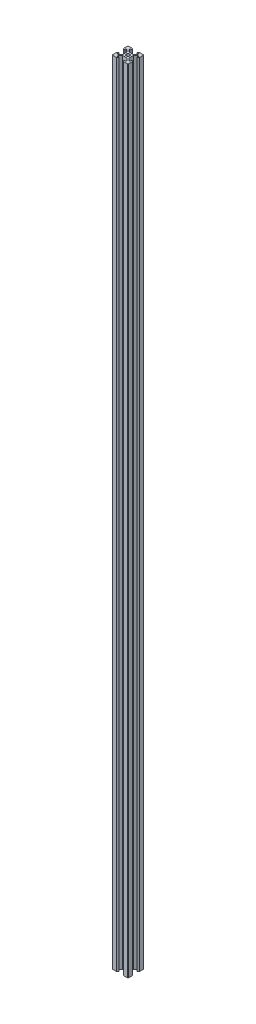
SolidWorks part; units mm, degrees
ref_plane "Front Plane" through (0, 0, 0) normal (0, 0, 1) x (1, 0, 0)
ref_plane "Top Plane" through (0, 0, 0) normal (0, 1, 0) x (1, 0, 0)
ref_plane "Right Plane" through (0, 0, 0) normal (1, 0, 0) x (0, 0, -1)
sketch "Sketch1" plane through (0, 0, 0) normal (0, 1, 0) x (1, 0, 0)
  line L0 (-2.1465, 12.2219) -> (22.938, 12.2219) construction
  line L1 (7.155, 13.9) -> (4.5, 16.555)
  line L2 (0.5, 0) -> (5.42, 0)
  line L3 (0, 0.5) -> (0, 5.42)
  line L4 (0.5, 20) -> (5.42, 20)
  line L5 (20, 0.5) -> (20, 19.5)
  line L6 (7.155, 13.9) -> (12.8341, 13.9)
  line L7 (6.1, 12.845) -> (6.1, 7.1491)
  line L8 (7.1445, 6.1) -> (12.8546, 6.1)
  line L9 (13.9, 12.8445) -> (13.9, 7.1491)
  line L10 (0, 20) -> (4.5, 20)
  line L11 (0, 20) -> (0, 15.5)
  line L12 (1.8, 15.5) -> (3.445, 15.5)
  line L13 (4.5, 18.2) -> (4.5, 16.555)
  line L14 (6.1, 12.845) -> (6.0943, 12.8393)
  line L15 (3.445, 15.5) -> (3.4393, 15.4943)
  line L16 (6.0943, 12.8393) -> (3.4393, 15.4943)
  line L17 (5.42, 20) -> (6.875, 18.545)
  line L18 (4.5, 20) -> (5.42, 20)
  line L19 (6.875, 20) -> (19.5, 20)
  line L20 (4.5, 18.2) -> (6.875, 18.2)
  line L21 (6.875, 20) -> (6.875, 18.2)
  line L22 (0, 14.58) -> (1.46, 13.12)
  line L23 (15.5, 18.2) -> (15.5, 16.555)
  line L24 (0, 15.5) -> (0, 13.12)
  line L25 (0, 13.12) -> (1.8, 13.12)
  line L26 (1.8, 15.5) -> (1.8, 13.12)
  line L27 (16.5507, 15.5) -> (18.2, 15.5)
  line L28 (15.5, 18.2) -> (13.12, 18.2)
  line L29 (13.12, 18.2) -> (13.12, 18.545)
  line L30 (13.12, 18.545) -> (14.575, 20)
  line L31 (18.2, 15.5) -> (18.2, 13.12)
  line L32 (18.2, 13.12) -> (18.5344, 13.12)
  line L33 (18.5344, 13.12) -> (20, 14.58)
  line L34 (12.8341, 13.9) -> (15.5, 16.555)
  line L35 (18.2, 4.5) -> (16.5585, 4.5)
  line L36 (16.5507, 15.5) -> (16.5585, 15.4922)
  line L37 (13.8926, 12.8372) -> (16.5585, 15.4922)
  line L38 (15.5, 3.4377) -> (15.5, 1.8)
  line L39 (18.2, 4.5) -> (18.2, 6.88)
  line L40 (18.2, 6.88) -> (18.6069, 6.88)
  line L41 (20, 5.42) -> (18.6069, 6.88)
  line L42 (15.5, 1.8) -> (13.12, 1.8)
  line L43 (13.12, 1.8) -> (13.12, 1.455)
  line L44 (14.575, 0) -> (13.12, 1.455)
  line L45 (13.9, 7.1491) -> (16.5585, 4.5)
  line L46 (12.8546, 6.1) -> (12.8412, 6.0865)
  line L47 (15.5, 3.4377) -> (15.4997, 3.4375)
  line L48 (12.8412, 6.0865) -> (15.4997, 3.4375)
  line L49 (1.8, 4.5) -> (3.4393, 4.5)
  line L50 (4.5, 3.4393) -> (4.5, 1.8)
  line L51 (1.46, 6.88) -> (1.8, 6.88)
  line L52 (1.8, 6.88) -> (1.8, 4.5)
  line L53 (0, 5.42) -> (1.46, 6.88)
  line L54 (4.5, 1.8) -> (6.875, 1.8)
  line L55 (6.875, 1.8) -> (6.875, 1.455)
  line L56 (5.42, 0) -> (6.875, 1.455)
  line L57 (3.4393, 4.5) -> (6.1, 7.1491)
  line L58 (14.575, 0) -> (19.5, 0)
  line L59 (7.1445, 6.1) -> (7.1583, 6.0861)
  line L60 (4.4977, 3.437) -> (7.1583, 6.0861)
  line L61 (0, 6.88) -> (0, 19.5)
  circle A0 centre (10, 10) radius 2.0746
  arc A1 (0.5, 0) -> (0, 0.5) centre (0.5, 0.5) cw
  arc A2 (19.5, 0) -> (20, 0.5) centre (19.5, 0.5) ccw
  arc A3 (19.5, 20) -> (20, 19.5) centre (19.5, 19.5) cw
  arc A4 (0, 19.5) -> (0.5, 20) centre (0.5, 19.5) cw
  point P22 (0, 0)
  point P25 (20, 0)
  dimension "D14" = 0.5
  dimension "D1" = 20
  dimension "D2" = 20
  dimension "D3" = 10
  dimension "D4" = 10
  dimension "D5" = 7.8
  dimension "D6" = 7.8
  dimension "D7" = 3.9
  dimension "D8" = 3.9
  dimension "D9" = 4.5
  dimension "D10" = 4.5
  dimension "D11" = 45
  dimension "D12" = 1.5
  dimension "D13" = 1.5
  dimension "D15" = 2.375
  dimension "D16" = 1.8
  dimension "D17" = 9.155
  dimension "D18" = 45
  dimension "D19" = 2.38
  dimension "D20" = 1.8
  dimension "D21" = 4.58
  dimension "D22" = 45
  dimension "D24" = 2.38
  dimension "D25" = 2.38
  dimension "D27" = 2.38
  dimension "D28" = 9.16
  dimension "D29" = 4.58
  dimension "D30" = 2.38
  dimension "D31" = 1.8
  dimension "D32" = 45
  dimension "D33" = 1.5
  dimension "D34" = 2.38
  dimension "D35" = 45
  dimension "D36" = 4.58
  dimension "D37" = 2.375
  dimension "D39" = 45
  dimension "D40" = 4.58
  dimension "D41" = 1.5
extrude "Boss-Extrude2" add sketch "Sketch1" along normal blind 1000 contours L7 L0 L9 L37 L36 L27 L31 L32 L33 L5 A3 L19 L30 L29 L28 L23 L34 L6 L1 L13 L20 L21 L17 L4 A4 L11 L24 L22 L25 L26 L12 L15 L16 L14 | L0 L7 L57 L49 L52 L51 L53 L3 A1 L2 L56 L55 L54 L50 L60 L59 L8 L46 L48 L47 L38 L42 L43 L44 L58 A2 L5 L41 L40 L39 L35 L45 L9 A0 region at (6.3146, 0, -12.5334) region at (10, 0, -12.1984)
ref_axis "Eje1" through (10, 1006.0887, -10) along (0, -1, 0)
ref_plane "Plano1" through (0, 0, -10) normal (0, 0, -1) x (-1, 0, 0)
ref_plane "Plano2" through (0, 500, 0) normal (0, -1, 0) x (-1, 0, 0)
ref_plane "Plano3" through (10, 0, 0) normal (1, 0, 0) x (0, 0, -1)
